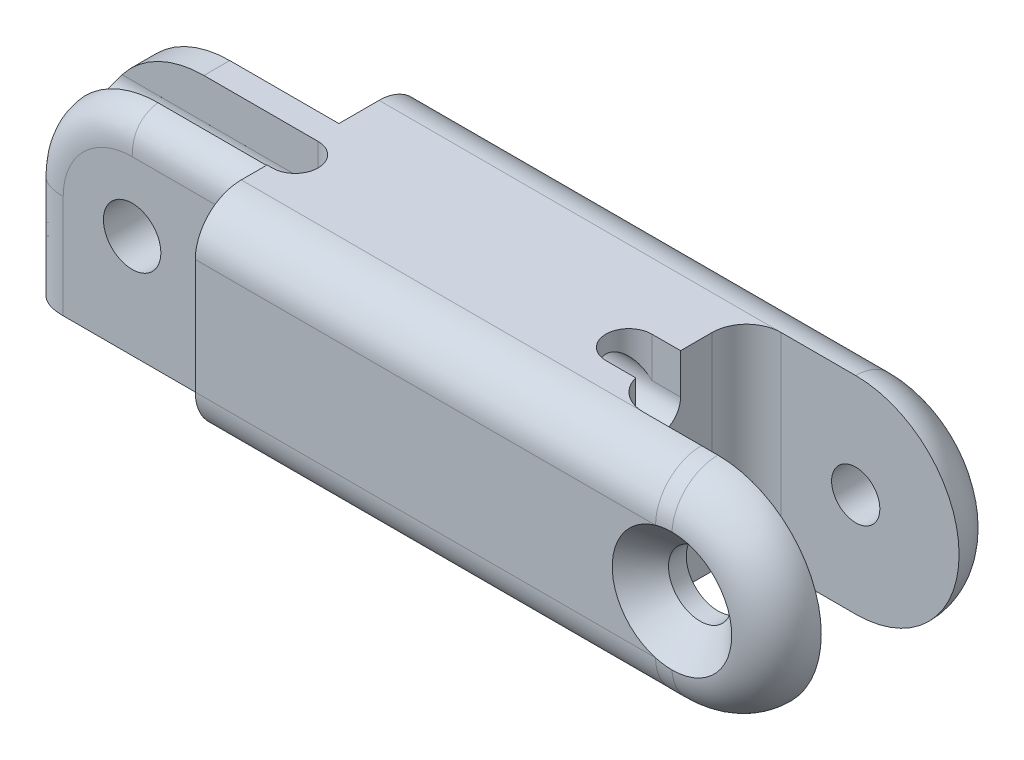
SolidWorks part; units mm, degrees
ref_plane "Front Plane" through (0, 0, 0) normal (0, 0, 1) x (1, 0, 0)
ref_plane "Top Plane" through (0, 0, 0) normal (0, 1, 0) x (1, 0, 0)
ref_plane "Right Plane" through (0, 0, 0) normal (1, 0, 0) x (0, 0, -1)
sketch "Sketch2" plane through (0, 0, 0) normal (0, 1, 0) x (1, 0, 0)
  line L0 (-16, 10) -> (34.5, 10)
  line L1 (34.5, 10) -> (34.5, 6)
  line L2 (34.5, 6) -> (19, 6)
  line L3 (16, 3) -> (16, -3)
  line L4 (19, -6) -> (34.5, -6)
  line L5 (34.5, -6) -> (34.5, -10)
  line L7 (-34.5, -6) -> (-34.5, 2.5)
  line L8 (-49.3622, 0) -> (56.3776, 0) construction
  line L9 (0, 21.2372) -> (0, -19.0689) construction
  line L10 (16, 3) -> (19, 3) construction
  line L11 (19, 3) -> (19, 6) construction
  line L16 (-16, -10) -> (34.5, -10)
  line L18 (-34.5, -6) -> (-16, -6)
  line L19 (-16, -6) -> (-16, -10)
  line L20 (-34.5, 2.5) -> (-16, 2.5)
  line L21 (-16, 2.5) -> (-16, 10)
  arc A0 (19, 6) -> (16, 3) centre (19, 3) ccw
  arc A1 (19, -6) -> (16, -3) centre (19, -3) cw
  point P13 (19, 3)
  dimension "D1" = 69
  dimension "D2" = 20
  dimension "D3" = 4
  dimension "D4" = 18.5
  dimension "D5" = 12
  dimension "D6" = 3
  dimension "D7" = 3
  dimension "D8" = 7.5
  dimension "D9" = 4
  dimension "D10" = 8.5
  dimension "D11" = 18.5
extrude "Boss-Extrude1" add sketch "Sketch2" along normal blind 18
sketch "Sketch5" plane through (0, 0, 10) normal (0, 0, 1) x (1, 0, 0)
  line L0 (-34.5, 9) -> (31.8491, 9) construction
  line L1 (-25.5, 18) -> (-25.5, 0) construction
  line L2 (34.5, 18) -> (34.5, 0) construction
  line L3 (-16, 18) -> (34.5, 18) construction
  line L4 (25.5, 18) -> (25.5, 0) construction
  line L5 (-34.5, 18) -> (-34.5, 0) construction
  line L6 (-34.5, 9) -> (-34.5, 0)
  line L7 (-34.5, 18) -> (-16, 18) construction
  line L8 (-34.5, 0) -> (25.5, 0)
  line L9 (-25.5, 18) -> (25.5, 18)
  arc A0 (-25.5, 18) -> (-34.5, 9) centre (-25.5, 9) ccw
  arc A1 (25.5, 0) -> (25.5, 18) centre (25.5, 9) ccw
  circle A2 centre (-25.5, 9) radius 2.5
  dimension "D2" = 5
  dimension "D1" = 9
extrude "Cut-Extrude1" cut sketch "Sketch5" against normal blind 20 flip side to cut
sketch "Sketch6" plane through (0, 0, 10) normal (0, 0, 1) x (1, 0, 0)
  line L0 (25.5, 0) -> (25.5, 18) construction
  point P4 (25.5, 9)
hole_wizard "CSK for M5 Countersunk Flat Head Screw1" positions "Sketch7" profile "Sketch8" countersink size "M5" standard "DIN" end condition up to next
sketch "Sketch7" plane through (0, 0, 10) normal (0, 0, 1) x (1, 0, 0)
  point P0 (25.5, 9)
sketch "Sketch8" plane through (25.5, 9, 10) normal (1, 0, 0) x (0, -1, 0)
  line L0 (0, 0) -> (0, 4)
  line L1 (0, 4) -> (2.75, 4)
  line L2 (2.75, 4) -> (2.75, 2.45)
  line L3 (2.75, 2.45) -> (5.2, 0)
  line L5 (5.2, 0) -> (0, 0)
  line L6 (-2.75, 2.45) -> (-5.2, 0) construction
  line L11 (0, -6.35) -> (0, 107.95) construction
  dimension "Thru Hole Dia." = 5.5
  dimension "Thru Hole Depth" = 4
  dimension "Near C'Sink Dia." = 10.4
  dimension "Near C'Sink Angle" = 90
hole_wizard "M5 Tapped Hole1" positions "Sketch9" profile "Sketch11" tap size "M5" standard "DIN" end condition through all
sketch "Sketch9" plane through (0, 0, 10) normal (0, 0, 1) x (1, 0, 0)
  point P0 (25.5, 9)
sketch "Sketch11" plane through (25.5, 9, 10) normal (1, 0, 0) x (0, -1, 0)
  line L0 (0, 0) -> (0, 20)
  line L1 (0, 20) -> (2.1, 20)
  line L2 (2.1, 20) -> (2.1, 3.1)
  line L3 (2.1, 3.1) -> (5.2, 0)
  line L5 (5.2, 0) -> (0, 0)
  line L6 (-2.1, 3.1) -> (-5.2, 0) construction
  line L11 (0, -6.35) -> (0, 107.95) construction
  dimension "Thru Tap Drill Dia." = 4.2
  dimension "Thru Tap Drill Depth" = 20
  dimension "Near C'Sink Dia." = 10.4
  dimension "Near C'Sink Angle" = 90
cosmetic thread "Hole Thread1" parameters "D2"=5
fillet "Fillet1" radius 4 2 edges at (4.75, 0, 10) (4.75, 18, 10)
fillet "Fillet2" radius 4 3 edges at (4.75, 0, -10) (34.5, 9, -10) (4.75, 18, -10)
fillet "Fillet3" radius 3 3 edges at (-34.5, 4.5, 6) (-20.75, 18, 6) (-31.864, 15.364, 6) conic rho 0.5
sketch "Sketch13" plane through (16, 0, 0) normal (1, 0, 0) x (0, 0, -1)
  line L0 (-1.75, 21.4915) -> (-1.75, -4.5302) construction
  line L1 (-3, 18) -> (3, 18) construction
  circle A0 centre (-1.75, 14.5) radius 2
  dimension "D2" = 4
  dimension "D3" = 3.5
  dimension "D1" = 1.75
extrude "Cut-Extrude2" cut sketch "Sketch13" against normal through all both and the other way through all
sketch "Sketch14" plane through (0, 18, 0) normal (0, 1, 0) x (1, 0, 0)
  line L0 (-32.6236, 0.2504) -> (-15.5557, 0.2504)
  line L1 (-32.5557, -3.75) -> (-15.5557, -3.75)
  line L3 (-32.5557, -3.75) -> (-32.6236, 0.2504)
  arc A0 (-15.5557, -3.75) -> (-15.5557, 0.2504) centre (-15.5557, -1.7498) ccw
  spline S1 degree 3 poles (-31.0797, -3) (-30.9473, -2.8693) (-30.8242, -2.7233) (-30.6669, -2.4679) (-30.62, -2.3776) (-30.5431, -2.1872) (-30.5127, -2.0851) (-30.4764, -1.8774) (-30.4703, -1.7698) (-30.4841, -1.5572) (-30.5036, -1.4537) (-30.5944, -1.1509) (-30.6934, -0.9724) (-30.9222, -0.6565) (-31.0506, -0.5207) (-31.3219, -0.2789) (-31.4619, -0.1762) (-31.8834, 0.0849) (-32.1717, 0.1991) (-32.5706, 0.2557) (-32.7006, 0.2556) (-32.9459, 0.209) (-33.0594, 0.1634) (-33.269, 0.0188) (-33.3624, -0.0793) (-33.5226, -0.3256) (-33.5911, -0.4779) (-33.6703, -0.7331) (-33.6932, -0.8231) (-33.7322, -1.0133) (-33.7481, -1.1133) (-33.7724, -1.3157) (-33.781, -1.419) (-33.7912, -1.6301) (-33.7926, -1.7379) (-33.7863, -2.055) (-33.7677, -2.2665) (-33.7021, -2.6575) (-33.6546, -2.8399) (-33.5922, -3) knots 0 0 0 0 0.0625 0.0625 0.09375 0.09375 0.125 0.125 0.15625 0.15625 0.1875 0.1875 0.25 0.25 0.3125 0.3125 0.375 0.375 0.5 0.5 0.5625 0.5625 0.625 0.625 0.6875 0.6875 0.75 0.75 0.78125 0.78125 0.8125 0.8125 0.84375 0.84375 0.875 0.875 0.9375 0.9375 1 1 1 1 construction
  spline S2 degree 3 poles (-33.5922, -3) (-33.5381, -3.1387) (-33.4701, -3.2552) (-33.3108, -3.4526) (-33.2195, -3.5323) (-33.0254, -3.6532) (-32.9205, -3.6957) (-32.705, -3.7461) (-32.594, -3.7546) (-32.2507, -3.7337) (-32.0173, -3.6588) (-31.5422, -3.4019) (-31.3092, -3.2263) (-31.0797, -3) knots 0 0 0 0 0.125 0.125 0.25 0.25 0.375 0.375 0.5 0.5 0.75 0.75 1 1 1 1 construction
  dimension "D2" = 2.0002
  dimension "D1" = 17
extrude "Cut-Extrude3" cut sketch "Sketch14" against normal blind 3.5
sketch "Sketch15" plane through (0, 18, 0) normal (0, 1, 0) x (1, 0, 0)
sketch "Sketch16" plane through (0, 18, 0) normal (0, 1, 0) x (1, 0, 0)
  line L0 (-8.0769, -1.75) -> (29.6251, -1.75) construction
  line L1 (13.5, 0.25) -> (19.0559, 0.25)
  line L3 (13.5, -3.75) -> (19.0559, -3.75)
  line L4 (19.0559, 0.25) -> (19.0559, -3.75)
  line L5 (16, -3) -> (16, 3) construction
  arc A0 (13.5, 0.25) -> (13.5, -3.75) centre (13.5, -1.75) ccw
  dimension "D2" = 4
  dimension "D1" = 1.75
  dimension "D3" = 2.5
extrude "Cut-Extrude4" cut sketch "Sketch16" against normal blind 3.5
